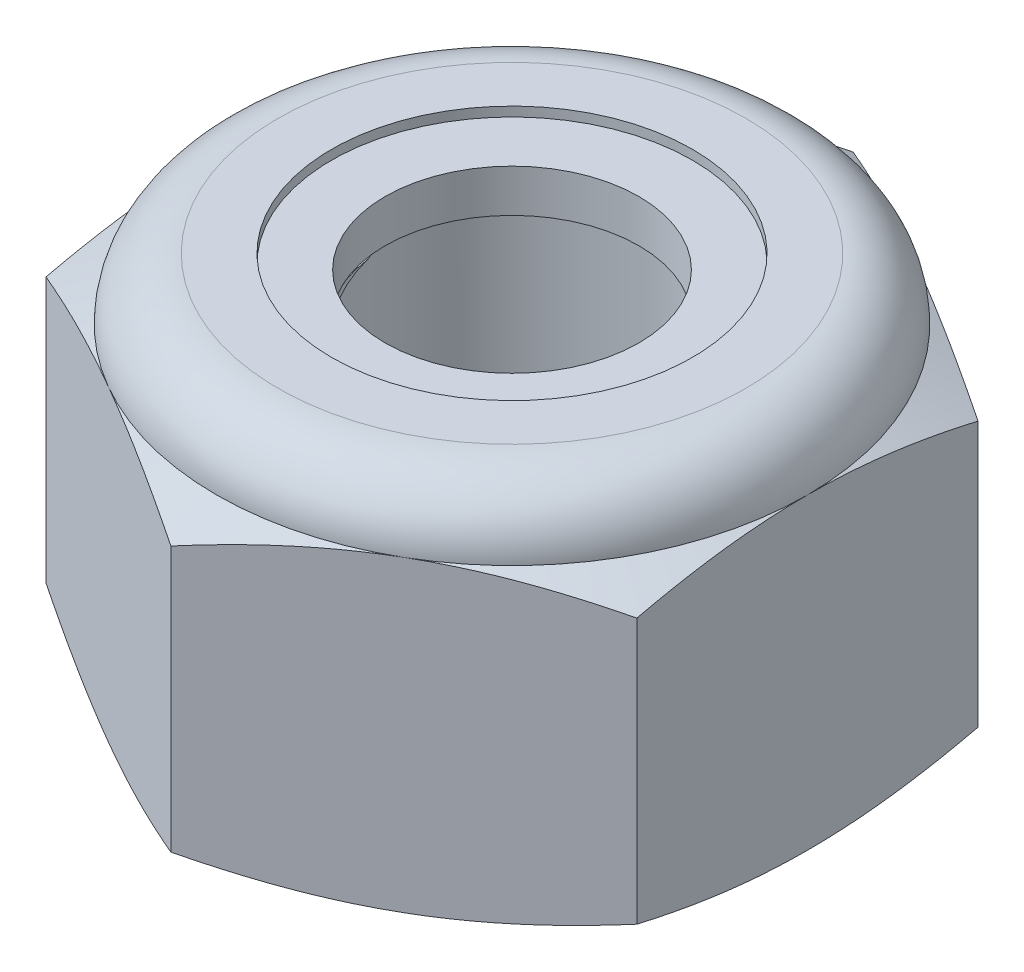
SolidWorks part; units mm, degrees
material "Alloy Steel"
ref_plane "Front" through (0, 0, 0) normal (0, 0, 1) x (1, 0, 0)
ref_plane "Top" through (0, 0, 0) normal (0, 1, 0) x (1, 0, 0)
ref_plane "Right" through (0, 0, 0) normal (1, 0, 0) x (0, 0, -1)
sketch "Sketch1" plane through (0, 0, 0) normal (0, 1, 0) x (1, 0, 0)
  line L1 (0, 5.4993) -> (-4.7625, 2.7496)
  line L2 (-4.7625, 2.7496) -> (-4.7625, -2.7496)
  line L3 (-4.7625, -2.7496) -> (0, -5.4993)
  line L4 (0, -5.4993) -> (4.7625, -2.7496)
  line L5 (4.7625, -2.7496) -> (4.7625, 2.7496)
  line L6 (4.7625, 2.7496) -> (0, 5.4993)
  circle A0 centre (0, 0) radius 4.7625 construction
  dimension "Hex Flats" = 9.525
extrude "Extrude1" add sketch "Sketch1" along normal blind 5.9531
sketch "Sketch2" plane through (0, 0, 0) normal (1, 0, 0) x (0, 0, -1)
  line L0 (-2.413, 0) -> (-2.413, 5.9531) construction
  line L1 (0, 0) -> (2.413, 0)
  line L2 (0, 0) -> (0, 5.9531)
  line L3 (0, 5.9531) -> (2.413, 5.9531)
  line L4 (2.413, 0) -> (2.413, 5.9531)
  line L5 (-2.7496, 5.9531) -> (2.7496, 5.9531) construction
  line L7 (0, -2.413) -> (0, 0) construction
  dimension "Thread Dia" = 4.826
revolve "Revolve1" add sketch "Sketch2" angle 360 about L7
sketch "Sketch3" plane through (0, 0, 0) normal (1, 0, 0) x (0, 0, -1)
  line L0 (2.413, 5.9531) -> (-2.413, 5.9531) construction
  line L1 (-2.413, 5.9531) -> (-2.413, 5.1594) construction
  line L2 (-2.413, 5.1594) -> (2.413, 5.9531) construction
  line L3 (2.413, 5.9531) -> (2.4291, 5.8552) construction
  line L4 (2.4291, 5.8552) -> (2.5418, 5.1699)
  line L5 (2.5418, 5.1699) -> (2.0776, 5.3449)
  line L6 (2.0776, 5.3449) -> (2.0454, 5.5407)
  line L7 (2.0454, 5.5407) -> (2.4291, 5.8552)
  line L8 (2.0615, 5.4428) -> (2.4855, 5.5126) construction
  line L9 (2.413, 5.9531) -> (2.413, 5.5006) construction
  line L10 (2.413, 5.5006) -> (-2.413, 4.7069) construction
  line L11 (-2.413, 4.7069) -> (-2.413, 5.1594) construction
  line L12 (-0.1397, 5.9531) -> (0.1397, 4.2544) construction
  line L13 (-2.413, 0) -> (-2.413, 5.9531) construction
  line L14 (0, 5.9531) -> (2.413, 5.9531) construction
  line L15 (2.413, 0) -> (2.413, 5.9531) construction
  point P13 (0, 5.1038)
  dimension "D1" = 0.0992
  dimension "D2" = 0.1984
  dimension "Thread Pitch" = 0.7937
  dimension "D4" = 60
  dimension "D5" = 0.7937
revolve "Cut-Revolve1" cut sketch "Sketch3" angle 360 about L12
pattern_linear "LPattern1" [suppressed] count 8 spacing 0.7937 along (0, -1, 0) count 2 spacing 0.7937 along (0, 1, 0) of bodies 110
sketch "Sketch4" plane through (0, 0, 0) normal (1, 0, 0) x (0, 0, -1)
  line L0 (0, 5.9531) -> (2.413, 5.9531)
  line L1 (2.413, 5.9531) -> (2.0454, 5.7817)
  line L2 (2.0454, 5.7817) -> (2.0454, 0.1714)
  line L3 (2.0454, 0.1714) -> (2.413, 0)
  line L4 (2.413, 0) -> (0, 0)
  line L5 (0, 0) -> (0, 5.9531)
  line L6 (2.413, 0) -> (2.413, 5.9531) construction
  line L7 (0, 5.9531) -> (2.413, 5.9531) construction
  line L8 (0, 0) -> (2.413, 0) construction
  line L9 (0, 0) -> (0, 5.9531) construction
  line L10 (0, 5.9531) -> (0, 6.3587) construction
  dimension "D1" = 25
revolve "Cut-Revolve2" [suppressed] cut sketch "Sketch4" angle 360 about L10
combine bodies "Combine1" operation type subtract main body 108 bodies to subtract 110
sketch "Sketch5" plane through (0, 0, 0) normal (1, 0, 0) x (0, 0, -1)
  line L0 (0, 0) -> (4.7625, 0)
  line L1 (4.7625, 0) -> (5.4993, 0.3436)
  line L2 (5.4993, 0.3436) -> (5.4993, 4.6174)
  line L3 (5.4993, 4.6174) -> (4.7625, 4.9609)
  line L4 (3.7703, 5.9531) -> (3.7703, 7.2231)
  line L5 (3.7703, 7.2231) -> (6.7693, 7.2231)
  line L6 (6.7693, 7.2231) -> (6.7693, -1.27)
  line L7 (6.7693, -1.27) -> (0, -1.27)
  line L8 (0, -1.27) -> (0, 0)
  line L9 (4.7625, 4.9609) -> (4.7625, 0) construction
  line L10 (0, 0) -> (2.413, 0) construction
  line L13 (5.4993, 2.4805) -> (6.7693, 2.4805) construction
  line L14 (5.4993, 5.9531) -> (5.4993, 0) construction
  line L15 (0, 0) -> (0, 7.2231) construction
  line L20 (0, 7.2231) -> (3.7703, 7.2231) construction
  line L22 (0, 5.9531) -> (2.413, 5.9531) construction
  arc A0 (4.7625, 4.9609) -> (3.7703, 5.9531) centre (3.7703, 4.9609) ccw
  dimension "D1" = 25
  dimension "D2" = 1.27
  dimension "D3" = 5.9531
  dimension "D4" = 0.9922
revolve "Cut-Revolve3" cut sketch "Sketch5" angle 360 about L15
sketch "Sketch6" plane through (0, 0, 0) normal (1, 0, 0) x (0, 0, -1)
  line L0 (0, 4.9609) -> (4.6101, 4.9609)
  line L1 (3.7703, 5.8007) -> (2.9079, 5.8007)
  line L2 (0, 7.2231) -> (0, 4.9609)
  line L3 (2.9079, 7.2231) -> (0, 7.2231)
  line L4 (0, 7.2231) -> (3.7703, 7.2231) construction
  line L5 (0, 0) -> (0, 7.2231) construction
  line L6 (0, 7.2231) -> (0, 44.323) construction
  line L7 (2.9079, 5.8007) -> (2.9079, 7.2231)
  line L8 (3.7703, 5.9531) -> (3.7703, 5.8007) construction
  line L9 (2.9079, 5.8007) -> (2.0454, 5.8007) construction
  line L10 (2.0454, 5.8007) -> (2.0454, 5.7817) construction
  arc A0 (4.6101, 4.9609) -> (3.7703, 5.8007) centre (3.7703, 4.9609) ccw
  arc A1 (4.7625, 4.9609) -> (3.7703, 5.9531) centre (3.7703, 4.9609) ccw construction
  dimension "D1" = 0.1524
revolve "Cut-Revolve4" cut sketch "Sketch6" angle 360 about L6
sketch "Sketch7" plane through (0, 0, 0) normal (1, 0, 0) x (0, 0, -1)
  line L0 (2.0454, 5.0371) -> (4.5301, 5.0371)
  line L1 (3.7703, 5.7245) -> (2.0454, 5.7245)
  line L2 (2.0454, 5.7245) -> (2.0454, 5.0371)
  line L3 (2.0454, 5.0371) -> (0, 5.0371) construction
  line L4 (0, 5.0371) -> (0, 5.7245) construction
  line L5 (0, 5.7245) -> (2.0454, 5.7245) construction
  line L6 (2.0454, 5.0371) -> (2.0454, 4.9609) construction
  line L7 (0, 4.9609) -> (4.6101, 4.9609) construction
  line L8 (3.7703, 5.7245) -> (3.7703, 5.8007) construction
  arc A0 (4.5301, 5.0371) -> (3.7703, 5.7245) centre (3.7703, 4.9609) ccw
  arc A2 (4.6101, 4.9609) -> (3.7703, 5.8007) centre (3.7703, 4.9609) ccw construction
  dimension "D1" = 0.0762
revolve "Revolve2" add sketch "Sketch7" angle 360 about L4
equation "\"D1@Sketch3\"=\"Thread Pitch@Sketch3\"/8"
equation "\"D2@Sketch3\"=\"Thread Pitch@Sketch3\"/4"
equation "\"D5@Sketch3\"=\"Thread Pitch@Sketch3\""
equation "\"D4@LPattern1\"=\"Thread Pitch@Sketch3\""
equation "\"D3@LPattern1\"=\"Thread Pitch@Sketch3\""
equation "\"D1@LPattern1\"=\"Height@Extrude1\"/\"Thread Pitch@Sketch3\""
equation "\"D4@Sketch5\"=\"Height@Extrude1\"/6"
